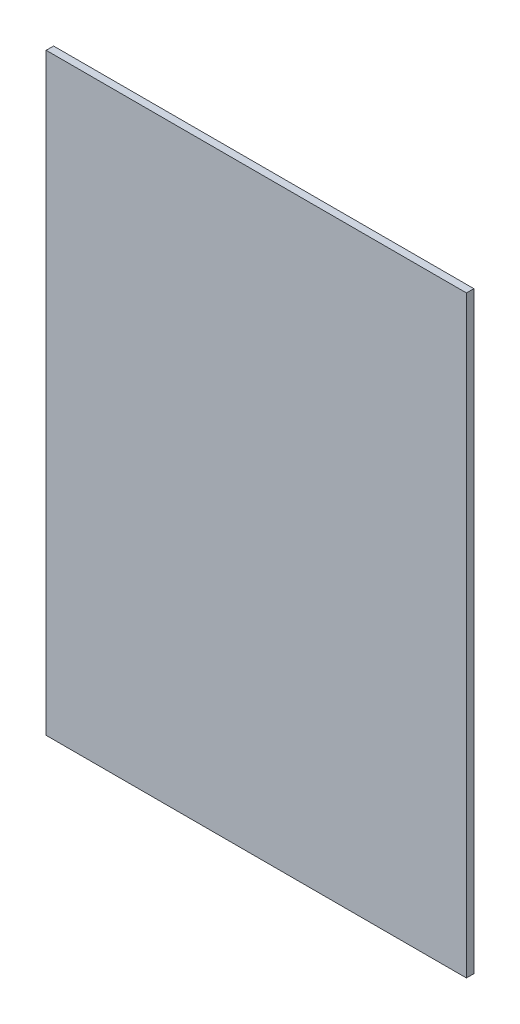
SolidWorks part; units mm, degrees
ref_plane "Plan de face" through (0, 0, 0) normal (0, 0, 1) x (1, 0, 0)
ref_plane "Plan de dessus" through (0, 0, 0) normal (0, 1, 0) x (1, 0, 0)
ref_plane "Plan de droite" through (0, 0, 0) normal (1, 0, 0) x (0, 0, -1)
sketch "Esquisse1" plane through (0, 0, 0) normal (0, 0, 1) x (1, 0, 0)
  line L1 (-65.6501, 67.6742) -> (104.3499, 67.6742)
  line L2 (-65.6501, 67.6742) -> (-65.6501, -172.3258)
  line L3 (-65.6501, -172.3258) -> (104.3499, -172.3258)
  line L4 (104.3499, 67.6742) -> (104.3499, -172.3258)
  dimension "D1" = 170
  dimension "D2" = 240
extrude "Boss.-Extru.1" add sketch "Esquisse1" along normal blind 3
equation "\"D1@Esquisse1\"=\"LongueurSyphon\""
equation "\"D2@Esquisse1\"=\"HauteurSyphon\""
equation "\"ProfondeurBoite\"=460"
equation "\"LongueurSyphon\"=170"
equation "\"LargeurSyphon\"=120"
equation "\"EpaisseurPlaque\"= 3"
equation "\"HauteurSyphon\"=\"HauteurCoteGauche\"-\"HauteurSolSyphon\""
equation "\"D1@Boss.-Extru.1\"=\"EpaisseurPlaque\""
equation "\"HauteurCoteDroit\"= 490"
equation "\"HauteurCoteGauche\"= 540"
equation "\"HauteurSolSyphon\"= 300"
equation "\"LargeurDroite\"=10"
equation "\"LargeurGauche\"=150"
equation "\"LargeurBoite\"= \"LargeurDroite\" + \"LargeurGauche\" + \"LargeurSyphon\""
